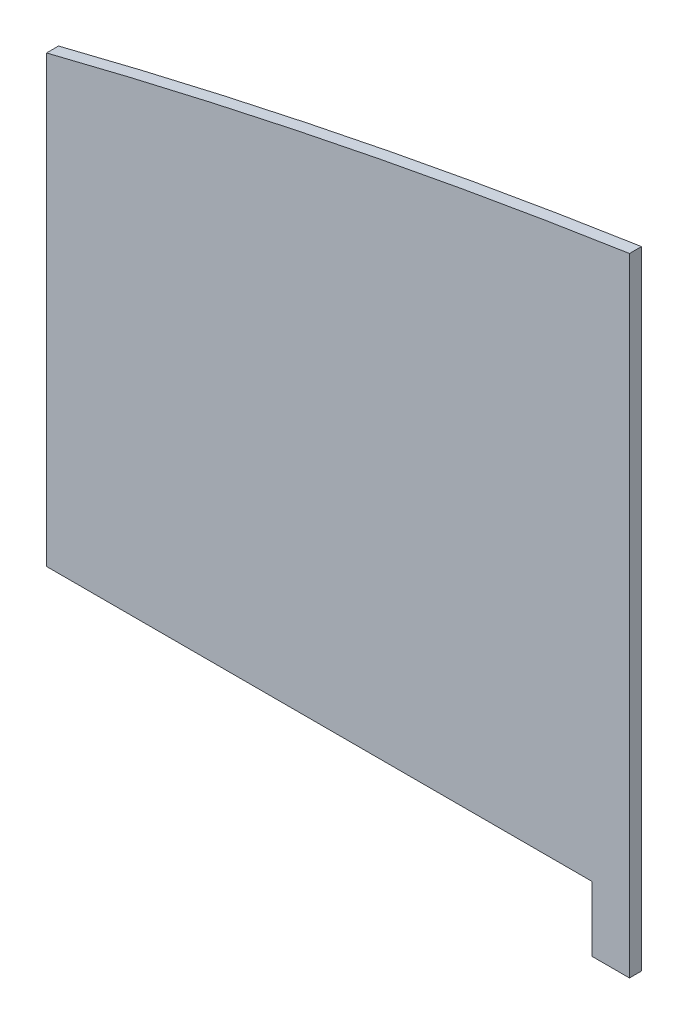
SolidWorks part; units mm, degrees
material "Hardox"
ref_plane "Ön Düzlem" through (0, 0, 0) normal (0, 0, 1) x (1, 0, 0)
ref_plane "Üst Düzlem" through (0, 0, 0) normal (0, 1, 0) x (1, 0, 0)
ref_plane "Sağ Düzlem" through (0, 0, 0) normal (1, 0, 0) x (0, 0, -1)
sketch "Çizim1" plane through (0, 0, 0) normal (0, 0, 1) x (1, 0, 0)
  line L0 (0, 0) -> (0, 370)
  line L2 (485, 468) -> (485, -54)
  line L3 (485, -54) -> (454, -54)
  line L4 (454, -54) -> (454, 0)
  line L5 (454, 0) -> (0, 0)
  line L6 (212.7416, -37.2685) -> (204.155, 454.6565) construction
  arc A0 (0, 370) -> (485, 468) centre (1226.1383, -4449.0057) cw
  dimension "D8" = 4972.5477
  dimension "D1" = 54
  dimension "D2" = 522
  dimension "D3" = 370
  dimension "D4" = 485
  dimension "D5" = 31
  dimension "D6" = 98
  dimension "D7" = 485
base flange "Taban-Flanş1" sketch "Çizim1" thickness 10 reverse thickness direction no parameters "D1"=4
sketch "Büküm-Çizgileri1" [suppressed] plane through (0, 0, 0) normal (0, 1, 0) x (1, 0, 0)
sketch "Sınırlandırma-Kutusu1" [suppressed] plane through (0, 0, 0) normal (0, 1, 0) x (1, 0, 0)
sheet metal parameters "Sac-Levha1" thickness 10 parameters "D1"=4
flat pattern "Düz-Çoğaltma1" [suppressed]
sketch "Büküm-Çizgileri2" plane through (0, 0, 0) normal (0, 1, 0) x (1, 0, 0)
sketch3d "Sınırlandırma-Kutusu2" [suppressed]
  line L0 (-741.1383, 4917.0057, 0) -> (-741.1383, 4395.0057, 0) construction
  line L1 (-1226.1383, 4917.0057, 0) -> (-1226.1383, 4395.0057, 0) construction
  line L2 (-741.1383, 4917.0057, 0) -> (-1226.1383, 4917.0057, 0) construction
  line L3 (-741.1383, 4395.0057, 0) -> (-1226.1383, 4395.0057, 0) construction
